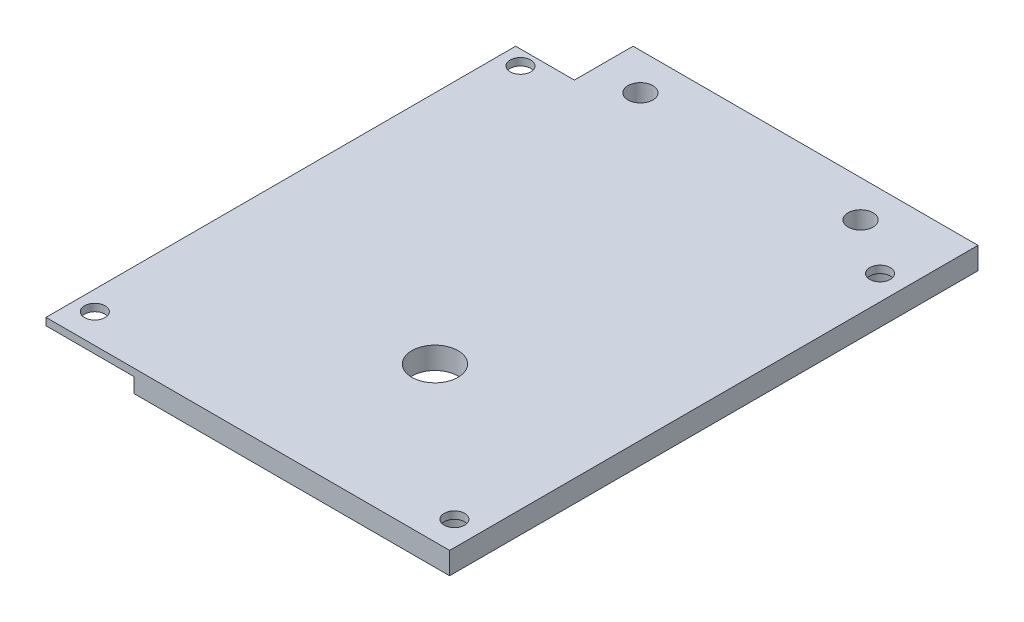
SolidWorks part; units mm, degrees
ref_plane "Plan de face" through (0, 0, 0) normal (0, 0, 1) x (1, 0, 0)
ref_plane "Plan de dessus" through (0, 0, 0) normal (0, 1, 0) x (1, 0, 0)
ref_plane "Plan de droite" through (0, 0, 0) normal (1, 0, 0) x (0, 0, -1)
sketch "Esquisse1" plane through (0, 0, 0) normal (0, 1, 0) x (1, 0, 0)
  line L0 (0, -55) -> (0, 55) construction
  line L1 (-29, 36) -> (26, 36)
  line L2 (-29, 36) -> (-29, -36)
  line L3 (-29, -36) -> (26, -36)
  line L4 (26, 36) -> (26, -36)
  line L5 (-55, 0) -> (55, 0) construction
  line L7 (-29, -36) -> (-17, -36)
  line L8 (-29, -36) -> (-29, 36)
  line L9 (-29, 36) -> (-17, 36)
  line L10 (-17, -36) -> (-17, 36)
  line L11 (-29, 36) -> (-21, 36)
  line L12 (-29, 36) -> (-29, 28)
  line L13 (-29, 28) -> (-21, 28)
  line L14 (-21, 36) -> (-21, 28)
  circle A0 centre (15, 31) radius 1.7
  circle A1 centre (-15, 31) radius 1.7
  circle A2 centre (-26.3479, 26) radius 1.4
  circle A3 centre (22.6521, 26) radius 1.4
  circle A4 centre (22.6521, -32) radius 1.4
  circle A5 centre (-26.3479, -32) radius 1.4
  circle A6 centre (3, -15) radius 3.15
  circle A7 centre (-26.3479, 26) radius 2.4
  circle A8 centre (22.6521, 26) radius 2.4
  circle A9 centre (22.6521, -32) radius 2.4
  circle A10 centre (-26.3479, -32) radius 2.4
  point P18 (26, 0)
  dimension "D1" = 3.4
  dimension "D2" = 3.4
  dimension "D6" = 2.8
  dimension "D7" = 2.8
  dimension "D8" = 2.8
  dimension "D9" = 2.8
  dimension "D17" = 6.3
  dimension "D19" = 4.8
  dimension "D20" = 4.8
  dimension "D21" = 4.8
  dimension "D22" = 4.8
  dimension "D3" = 30
  dimension "D4" = 49
  dimension "D5" = 58
  dimension "D10" = 11
  dimension "D11" = 55
  dimension "D12" = 5
  dimension "D13" = 5
  dimension "D14" = 46
  dimension "D15" = 15
  dimension "D16" = 3
  dimension "D18" = 4
  dimension "D23" = 2
  dimension "D24" = 6
  dimension "D25" = 8
extrude "Boss.-Extru.3" add sketch "Esquisse1" along normal blind 3 contours L10 A1 L3 L4 L1 A9 A8 A6 A0 | A7 A2 | A8 A3 | L3 L10 L1 L2 A10 A7 | A10 A5 | A9 A4 region at (-22.6772, 0, 2.5102) region at (4.3245, 0, -0.0044) region at (-26.3479, 0, -27.9349) region at (20.32, 0, -26) region at (20.32, 0, 32) region at (-28.68, 0, 32)
extrude "Enlèv. mat.-Extru.7" cut sketch "Esquisse1<5>" along normal blind 2 contours A10 A5 | A9 A4 | A7 A2 | A8 A3 | L3 L10 L1 L2 A10 A7 region at (-22.6772, 0, 2.5102) region at (-26.3479, 0, -27.9349) region at (20.32, 0, -26) region at (20.32, 0, 32) region at (-28.68, 0, 32)
sketch "Esquisse1<5>" plane through (0, 0, 0) normal (0, 1, 0) x (1, 0, 0) same geometry as "Esquisse1"
equation "\"D2@Esquisse1\"=\"D1@Esquisse1\""
equation "\"D7@Esquisse1\"=\"D6@Esquisse1\""
equation "\"D8@Esquisse1\"=\"D6@Esquisse1\""
equation "\"D9@Esquisse1\"=\"D6@Esquisse1\""
equation "\"D20@Esquisse1\"=\"D19@Esquisse1\""
equation "\"D21@Esquisse1\"=\"D19@Esquisse1\""
equation "\"D22@Esquisse1\"=\"D19@Esquisse1\""
